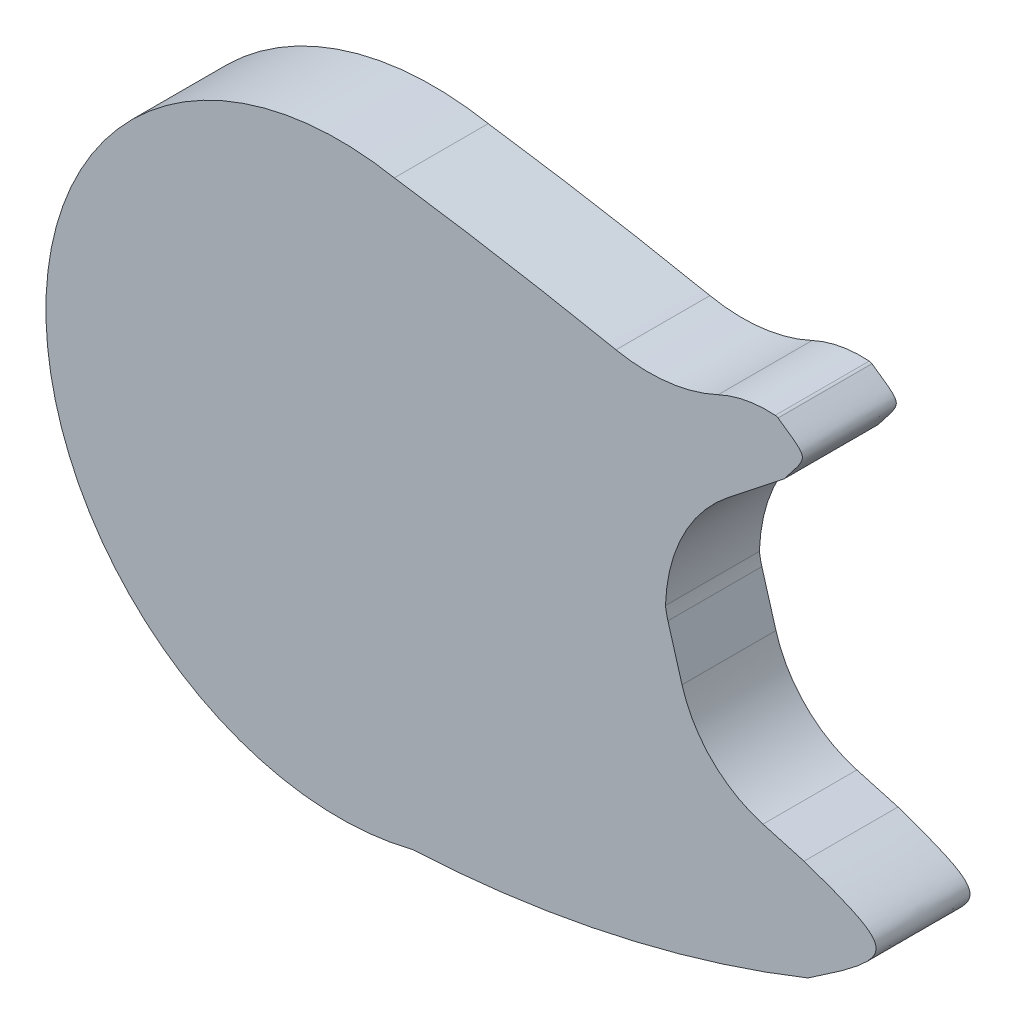
SolidWorks part; units mm, degrees
note: The reader was unsure of these and kept them because the rebuilt part matched: shared geometry of "Sketch2<3>".
material "AISI 321 Annealed Stainless Steel (SS)"
ref_plane "Front Plane" through (0, 0, 0) normal (0, 0, 1) x (1, 0, 0)
ref_plane "Top Plane" through (0, 0, 0) normal (0, 1, 0) x (1, 0, 0)
ref_plane "Right Plane" through (0, 0, 0) normal (1, 0, 0) x (0, 0, -1)
sketch "Sketch1" plane through (0, 0, 0) normal (0, 0, 1) x (1, 0, 0)
  line L0 (1.8944, 0.9481) -> (1.6555, 0.7598)
  line L1 (1.3891, 0.1903) -> (1.3873, 0.2522)
  line L2 (1.3992, 0.1767) -> (1.4591, -0.0292)
  line L3 (1.8039, -0.3707) -> (1.9788, -0.4199)
  circle A0 centre (0, 0) radius 1.25
  arc A1 (1.8565, 1.1635) -> (1.6131, 1.1177) centre (1.824, 0.6663) ccw
  arc A2 (1.8682, 1.1595) -> (1.8565, 1.1635) centre (1.8549, 1.1399) ccw
  arc A3 (1.6555, 0.7598) -> (1.3891, 0.1903) centre (2.0888, 0.21) ccw
  arc A4 (1.4591, -0.0292) -> (1.8039, -0.3707) centre (1.9392, 0.1106) ccw
  arc A5 (1.3873, 0.2522) -> (1.3992, 0.1767) centre (1.6872, 0.2606) ccw
  arc A6 (1.178, 1.0658) -> (0.2338, 1.2279) centre (-2.0496, -14.8939) ccw
  arc A7 (1.9957, -0.8423) -> (0.3091, -1.2112) centre (0.0516, 4.0064) cw
  arc A8 (1.6131, 1.1177) -> (1.178, 1.0658) centre (1.3167, 1.7519) cw
  conic Q0 (1.9957, -0.8423) -> (1.9788, -0.4199) control (2.4108, -0.5679) rho 0.703964
  conic Q1 (1.8944, 0.9481) -> (1.8682, 1.1595) control (1.9957, 1.0731) rho 0.787659
  point P20 (0, 0)
  dimension "D1" = 0.7
  dimension "D2" = 0.7
  dimension "D3" = 0.5
  dimension "D4" = 2.5
  dimension "D5" = 0.3
extrude "Boss-Extrude1" add sketch "Sketch1" along normal blind 0.4
sketch "Sketch2" plane through (0, 0, 0) normal (0, 0, -1) x (-1, 0, 0)
  line L0 (-0.4705, 0.5841) -> (0.4705, -0.5841)
  line L1 (-0.5094, 0.5527) -> (0.4316, -0.6154)
  line L2 (-0.4316, 0.6154) -> (0.5094, -0.5527)
  circle A0 centre (0, 0) radius 0.75
  dimension "D3" = 1.5
  dimension "D1" = 0.05
  dimension "D2" = 0.05
extrude "Cut-Extrude1" cut sketch "Sketch2" against normal blind 0.02 contours L1 A0 | L2 A0
extrude "Cut-Extrude2" cut sketch "Sketch2<3>" against normal blind 0.05 contours L2 A0 L0 | L0 A0 L1
sketch "Sketch2<3>" plane through (0, 0, 0) normal (0, 0, -1) x (-1, 0, 0) same geometry as "Sketch2"
